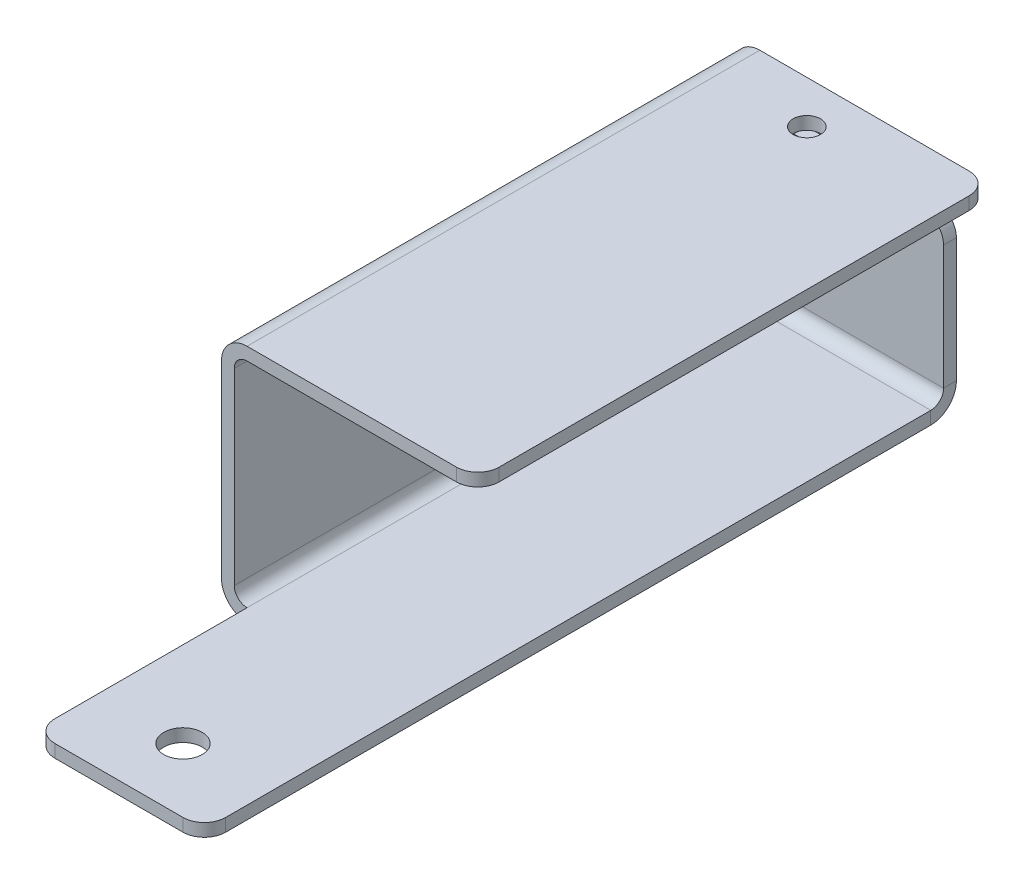
SolidWorks part; units mm, degrees
note: The reader was unsure of these and kept them because the rebuilt part matched: flange length of "Edge-Flange1", "Edge-Flange2", "Edge-Flange3".
ref_plane "Front Plane" through (0, 0, 0) normal (0, 0, 1) x (1, 0, 0)
ref_plane "Top Plane" through (0, 0, 0) normal (0, 1, 0) x (1, 0, 0)
ref_plane "Right Plane" through (0, 0, 0) normal (1, 0, 0) x (0, 0, -1)
sketch "Sketch1" plane through (0, 0, 0) normal (0, 1, 0) x (1, 0, 0)
  line L1 (10, -42.5) -> (-10, -42.5)
  line L2 (10, -42.5) -> (10, 42.5)
  line L3 (10, 42.5) -> (-10, 42.5)
  line L4 (-10, -42.5) -> (-10, 42.5)
  line L5 (10, -42.5) -> (-10, 42.5) construction
  line L6 (10, 42.5) -> (-10, -42.5) construction
  point P0 (0, 0)
  dimension "D1" = 20
  dimension "D2" = 85
base flange "Base-Flange1" sketch "Sketch1" thickness 1.5 reverse thickness direction no parameters "D1"=3
edge flange "Edge-Flange1" sketch "Sketch8" flange angle 90 flange length 25 flange position bend outside bend radius 1.5 thickness 1.5 relief rectangular parameters "D6"=10
sketch "Sketch8" plane through (-10, 0, 0) normal (-1, 0, 0) x (0, 0, 1)
  line L2 (-42.5, 0) -> (-42.5, 25)
  line L3 (-42.5, 25) -> (42.5, 25)
  line L4 (42.5, 25) -> (42.5, 0)
  line L7 (-42.5, 0) -> (42.5, 0) construction
  line L8 (-42.5, 0) -> (42.5, 0)
bend "EdgeBend1" bend radius 1.5 bend angle 90 parameters "D5"=1
edge flange "Edge-Flange2" sketch "Sketch11" flange angle 90 flange length 30 flange position material outside bend radius 1.5 thickness 1.5 relief rectangular parameters "D6"=10
sketch "Sketch11" plane through (-11.5, 25, 0) normal (0, 1, 0) x (0, 0, 1)
  line L2 (-42.5, 0) -> (-42.5, 28.5)
  line L3 (-42.5, 28.5) -> (42.5, 28.5)
  line L4 (42.5, 28.5) -> (42.5, 0)
  line L7 (42.5, 0) -> (-42.5, 0) construction
  line L8 (42.5, 0) -> (-42.5, 0)
bend "EdgeBend2" bend radius 1.5 bend angle 90 parameters "D5"=2
sketch "Sketch13" plane through (0, 0, 0) normal (1, 0, 0) x (0, 0, -1)
  line L0 (-42.5, 0) -> (42.5, 0) construction
  line L1 (-42.5, 0) -> (-17.5, 0)
  line L2 (-42.5, 0) -> (-42.5, 26.5)
  line L3 (-42.5, 26.5) -> (-17.5, 26.5)
  line L4 (-17.5, 0) -> (-17.5, 26.5)
  line L5 (-42.5, 0) -> (-17.5, 26.5) construction
  line L6 (-42.5, 26.5) -> (-17.5, 0) construction
  line L8 (-42.5, -1.5) -> (-42.5, 0) construction
  line L9 (-42.5, 1.5) -> (-42.5, 23.5) construction
  line L10 (-42.5, 26.5) -> (42.5, 26.5) construction
  point P0 (-30, 13.25)
  dimension "D2" = 25
extrude "Cut-Extrude1" cut sketch "Sketch13" against normal through all both and the other way through all
sketch "Sketch14" plane through (0, 0, 0) normal (0, 1, 0) x (1, 0, 0)
  line L1 (-10, -42.5) -> (-12.5981, -42.5)
  line L2 (-10, -42.5) -> (-10, -17.5)
  line L3 (-10, -17.5) -> (-12.5981, -17.5)
  line L4 (-12.5981, -42.5) -> (-12.5981, -17.5)
extrude "Cut-Extrude2" cut sketch "Sketch14" against normal through all both and the other way through all
sketch "Sketch15" plane through (0, 0, 0) normal (0, 1, 0) x (1, 0, 0)
  line L0 (-10, -42.5) -> (10, -42.5) construction
  circle A0 centre (0, -35) radius 2.25
  dimension "D1" = 4.5
  dimension "D2" = 7.5
extrude "cage mounting hole" cut sketch "Sketch15" against normal through all
edge flange "Edge-Flange3" sketch "Sketch18" flange angle 90 flange length 20 flange position bend outside bend radius 1.5 thickness 1.5 relief rectangular parameters "D6"=10
sketch "Sketch18" plane through (0, 0, -42.5) normal (0, 0, -1) x (-1, 0, 0)
  line L0 (-10, 0) -> (10, 0) construction
  line L1 (-10, 0) -> (10, 0)
  line L2 (-10, 0) -> (-10, 18.5)
  line L3 (-10, 18.5) -> (10, 18.5)
  line L4 (10, 18.5) -> (10, 0)
bend "EdgeBend3" bend radius 1.5 bend angle 90 parameters "D5"=3
sketch "Sketch19" plane through (0, 26.5, 0) normal (0, 1, 0) x (1, 0, 0)
  line L0 (17, 42.5) -> (-10, 42.5) construction
  circle A0 centre (0.5, 37.5) radius 1.6
  dimension "D1" = 3.2
  dimension "D2" = 0.5
  dimension "D3" = 5
extrude "arduino mounting hole" cut sketch "Sketch19" against normal up to next
fillet "Fillet1" radius 2.5 6 edges at (-10, -0.75, 42.5) (10, -0.75, 42.5) (-10, 18.5, -44.75) (10, 18.5, -44.75) (17, 25.75, -42.5) (17, 25.75, 17.5)
sketch "Bend-Lines1" [suppressed] plane through (0, 0, 0) normal (0, 1, 0) x (1, 0, 0)
sketch "Bounding-Box1" [suppressed] plane through (0, 0, 0) normal (0, 1, 0) x (1, 0, 0)
sheet metal parameters "Sheet-Metal1" thickness 1.5 parameters "D1"=3
flat pattern "Flat-Pattern1" [suppressed]
sketch "Bend-Lines2" plane through (0, 0, 0) normal (0, 1, 0) x (1, 0, 0)
sketch3d "Bounding-Box2" [suppressed]
  line L0 (10, 42.5, 0) -> (10, -42.5, 0) construction
  line L1 (-10, 42.5, 0) -> (-10, -42.5, 0) construction
  line L2 (10, 42.5, 0) -> (-10, 42.5, 0) construction
  line L3 (10, -42.5, 0) -> (-10, -42.5, 0) construction
sheet metal parameters "Sheet-Metal2" thickness 1.5 parameters "D1"=3
flat pattern "Flat-Pattern1"
sketch "Bend-Lines2" plane through (0, 0, 0) normal (0, 1, 0) x (1, 0, 0)
  line L0 (-12.1598, 42.5) -> (-12.1598, -42.5) construction
  line L1 (-12.1598, 42.5) -> (-12.1598, -42.5) construction
sketch3d "Bounding-Box2" [suppressed]
  line L0 (-35.8197, 42.5, 0) -> (-35.8197, -42.5, 0) construction
  line L1 (10, 42.5, 0) -> (10, -42.5, 0) construction
  line L2 (-35.8197, 42.5, 0) -> (10, 42.5, 0) construction
  line L3 (-35.8197, -42.5, 0) -> (10, -42.5, 0) construction
bend of the flat pattern "Flatten-<EdgeBend1>1"
sheet metal parameters "Sheet-Metal3" thickness 1.5 parameters "D1"=3
flat pattern "Flat-Pattern1"
sketch "Bend-Lines2" plane through (0, 0, 0) normal (0, 1, 0) x (1, 0, 0)
  line L0 (-12.1598, 42.5) -> (-12.1598, -42.5) construction
  line L1 (-12.1598, 42.5) -> (-12.1598, -42.5) construction
  line L2 (-37.2649, 42.5) -> (-37.2649, -42.5) construction
  line L3 (-37.2649, 42.5) -> (-37.2649, -42.5) construction
sketch3d "Bounding-Box2" [suppressed]
  line L0 (-65.7102, 42.5, 0) -> (-65.7102, -42.5, 0) construction
  line L1 (10, 42.5, 0) -> (10, -42.5, 0) construction
  line L2 (-65.7102, 42.5, 0) -> (10, 42.5, 0) construction
  line L3 (-65.7102, -42.5, 0) -> (10, -42.5, 0) construction
bend of the flat pattern "Flatten-<EdgeBend1>1"
bend of the flat pattern "Flatten-<EdgeBend2>1"
sheet metal parameters "Sheet-Metal4" thickness 1.5 parameters "D1"=3
flat pattern "Flat-Pattern1"
sketch "Bend-Lines2" plane through (-13.5, 0, 0) normal (-1, 0, 0) x (0, 0, 1)
  line L0 (17.5, -0.1598) -> (42.5, -0.1598) construction
  line L1 (17.5, -0.1598) -> (42.5, -0.1598) construction
  line L2 (17.5, 24.9452) -> (42.5, 24.9452) construction
  line L3 (17.5, 24.9452) -> (42.5, 24.9452) construction
sketch3d "Bounding-Box2" [suppressed]
  line L0 (17.5, 0.3273, 0) -> (17.5, 53.3905, 0) construction
  line L1 (42.5, 0.3273, 0) -> (42.5, 53.3905, 0) construction
  line L2 (17.5, 0.3273, 0) -> (42.5, 0.3273, 0) construction
  line L3 (17.5, 53.3905, 0) -> (42.5, 53.3905, 0) construction
bend of the flat pattern "Flatten-<EdgeBend1>1"
bend of the flat pattern "Flatten-<EdgeBend2>1"
sheet metal parameters "Sheet-Metal5" thickness 1.5 parameters "D1"=3
flat pattern "Flat-Pattern1"
sketch "Bend-Lines2" plane through (-13.5, 0, 0) normal (-1, 0, 0) x (0, 0, 1)
  line L0 (17.5, -0.1598) -> (-42.5, -0.1598) construction
  line L1 (17.5, -0.1598) -> (-42.5, -0.1598) construction
  line L2 (-42.5, 24.9452) -> (17.5, 24.9452) construction
  line L3 (-42.5, 24.9452) -> (17.5, 24.9452) construction
sketch3d "Bounding-Box2" [suppressed]
  line L0 (42.5, 53.3905, 0) -> (-42.5, 53.3905, 0) construction
  line L1 (42.5, -22.3197, 0) -> (-42.5, -22.3197, 0) construction
  line L2 (42.5, 53.3905, 0) -> (42.5, -22.3197, 0) construction
  line L3 (-42.5, 53.3905, 0) -> (-42.5, -22.3197, 0) construction
bend of the flat pattern "Flatten-<EdgeBend1>1"
bend of the flat pattern "Flatten-<EdgeBend2>1"
sheet metal parameters "Sheet-Metal6" thickness 1.5 parameters "D1"=3
flat pattern "Flat-Pattern1"
sketch "Bend-Lines2" plane through (-13.5, 0, 0) normal (-1, 0, 0) x (0, 0, 1)
  line L0 (17.5, -0.1598) -> (-42.5, -0.1598) construction
  line L1 (17.5, -0.1598) -> (-42.5, -0.1598) construction
  line L2 (-42.5, 24.9452) -> (17.5, 24.9452) construction
  line L3 (-42.5, 24.9452) -> (17.5, 24.9452) construction
sketch3d "Bounding-Box2" [suppressed]
  line L0 (42.5, 53.3905, 0) -> (-42.5, 53.3905, 0) construction
  line L1 (42.5, -22.3197, 0) -> (-42.5, -22.3197, 0) construction
  line L2 (42.5, 53.3905, 0) -> (42.5, -22.3197, 0) construction
  line L3 (-42.5, 53.3905, 0) -> (-42.5, -22.3197, 0) construction
bend of the flat pattern "Flatten-<EdgeBend1>1"
bend of the flat pattern "Flatten-<EdgeBend2>1"
sheet metal parameters "Sheet-Metal7" thickness 1.5 parameters "D1"=3
flat pattern "Flat-Pattern1"
sketch "Bend-Lines2" plane through (-13.5, 0, 0) normal (-1, 0, 0) x (0, 0, 1)
  line L0 (17.5, -0.1598) -> (-42.5, -0.1598) construction
  line L1 (17.5, -0.1598) -> (-42.5, -0.1598) construction
  line L2 (-42.5, 24.9452) -> (17.5, 24.9452) construction
  line L3 (-42.5, 24.9452) -> (17.5, 24.9452) construction
  line L4 (-45.4452, -22.3197) -> (-45.4452, -2.3197) construction
  line L5 (-45.4452, -22.3197) -> (-45.4452, -2.3197) construction
sketch3d "Bounding-Box2" [suppressed]
  line L0 (42.5, 53.3905, 0) -> (-63.8905, 53.3905, 0) construction
  line L1 (42.5, -22.3197, 0) -> (-63.8905, -22.3197, 0) construction
  line L2 (42.5, 53.3905, 0) -> (42.5, -22.3197, 0) construction
  line L3 (-63.8905, 53.3905, 0) -> (-63.8905, -22.3197, 0) construction
bend of the flat pattern "Flatten-<EdgeBend1>1"
bend of the flat pattern "Flatten-<EdgeBend2>1"
bend of the flat pattern "Flatten-<EdgeBend3>1"
sheet metal parameters "Sheet-Metal8" thickness 1.5 parameters "D1"=3
flat pattern "Flat-Pattern1"
sketch "Bend-Lines2" plane through (-13, 0, 0) normal (-1, 0, 0) x (0, 0, 1)
  line L0 (17.5, -0.2671) -> (-42.5, -0.2671) construction
  line L1 (17.5, -0.2671) -> (-42.5, -0.2671) construction
  line L2 (-42.5, 25.2671) -> (17.5, 25.2671) construction
  line L3 (-42.5, 25.2671) -> (17.5, 25.2671) construction
  line L4 (-44.2671, -22.0343) -> (-44.2671, -2.0343) construction
  line L5 (-44.2671, -22.0343) -> (-44.2671, -2.0343) construction
sketch3d "Bounding-Box2" [suppressed]
  line L0 (42.5, 54.0343, 0) -> (-63.0343, 54.0343, 0) construction
  line L1 (42.5, -22.0343, 0) -> (-63.0343, -22.0343, 0) construction
  line L2 (42.5, 54.0343, 0) -> (42.5, -22.0343, 0) construction
  line L3 (-63.0343, 54.0343, 0) -> (-63.0343, -22.0343, 0) construction
bend of the flat pattern "Flatten-<EdgeBend1>1"
bend of the flat pattern "Flatten-<EdgeBend2>1"
bend of the flat pattern "Flatten-<EdgeBend3>1"
